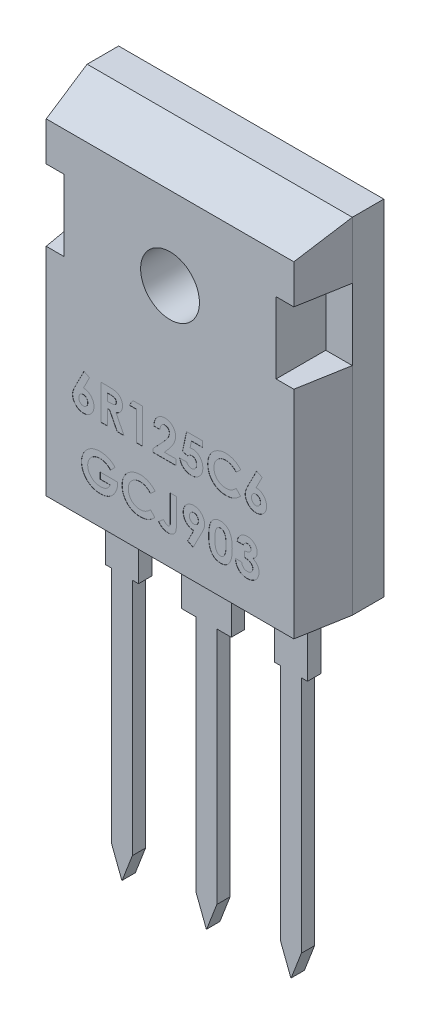
SolidWorks part; units mm, degrees
ref_plane "Front Plane" through (0, 0, 0) normal (0, 0, 1) x (1, 0, 0)
ref_plane "Top Plane" through (0, 0, 0) normal (0, 1, 0) x (1, 0, 0)
ref_plane "Right Plane" through (0, 0, 0) normal (1, 0, 0) x (0, 0, -1)
sketch "Sketch1" plane through (0, 0, 0) normal (0, 0, 1) x (1, 0, 0)
  line L0 (0, 6.1) -> (4.0279, 6.1) construction
  line L1 (-8, 10.4) -> (8, 10.4)
  line L2 (-8, 10.4) -> (-8, -10.4)
  line L3 (-8, -10.4) -> (8, -10.4)
  line L4 (8, 10.4) -> (8, -10.4)
  line L5 (-8, 10.4) -> (8, -10.4) construction
  line L6 (-8, -10.4) -> (8, 10.4) construction
  circle A0 centre (0, 4.325) radius 1.775
  point P0 (0, 0)
  point P10 (0, 0)
  dimension "D3" = 4.3
  dimension "D4" = 3.55
  dimension "D1" = 20.8
  dimension "D2" = 16
extrude "Boss-Extrude1" add sketch "Sketch1" against normal blind 1.9
sketch "Sketch2" plane through (0, 0, 0) normal (0, 0, 1) x (1, 0, 0)
  line L0 (0, 0) -> (0, 12.0952) construction
  line L1 (-8, 6.95) -> (-6.4, 6.95)
  line L2 (-8, 6.95) -> (-8, 2.65) construction
  line L3 (-8, 2.65) -> (-6.4, 2.65)
  line L4 (8, -10.4) -> (8, 10.4)
  line L5 (8, 10.4) -> (-8, 10.4)
  line L6 (-8, 10.4) -> (-8, -10.4)
  line L7 (-8, -10.4) -> (8, -10.4)
  line L8 (8, -10.4) -> (8, 2.65)
  line L9 (8, 10.4) -> (-8, 10.4)
  line L10 (-8, 10.4) -> (-8, 6.95)
  line L11 (-8, -10.4) -> (8, -10.4)
  line L12 (-6.4, 6.95) -> (-6.4, 2.65)
  line L13 (8, 2.65) -> (6.4, 2.65)
  line L14 (6.4, 6.95) -> (6.4, 2.65)
  line L15 (8, 6.95) -> (6.4, 6.95)
  line L16 (8, 6.95) -> (8, 2.65) construction
  line L17 (-8, 6.95) -> (-8, 2.65) construction
  line L18 (-8, 2.65) -> (-8, -10.4)
  line L19 (8, 2.65) -> (8, 6.95) construction
  line L20 (8, 6.95) -> (8, 10.4)
  circle A0 centre (0, 4.325) radius 1.775 construction
  circle A1 centre (0, 4.325) radius 1.775
  dimension "D2" = 12.8
  dimension "D3" = 3.45
  dimension "D4" = 4.3
  dimension "D1" = 0
extrude "Boss-Extrude2" add sketch "Sketch2" along normal blind 3 separate body
chamfer "Chamfer1" distance 3 angle 20 1 edges at (0, 10.4, 3) first distance on face at (0, 10.4, 1.5)
chamfer "Chamfer2" distance 3 angle 10 4 edges at (-8, -3.875, 3) (-8, 8.129, 3) (8, 8.129, 3) (8, -3.875, 3) first distance on face at (-8, -3.875, 1.5) first distance on face at (-8, 8.402, 1.5) first distance on face at (8, 8.402, 1.5) first distance on face at (8, -3.875, 1.5)
sketch "Sketch4" plane through (0, -10.4, 0) normal (0, -1, 0) x (1, 0, 0)
  line L0 (-8, 0) -> (8, 0) construction
  line L1 (-6.1, 0) -> (-4.1, 0)
  line L2 (-6.1, 0) -> (-6.1, 0.8)
  line L3 (-6.1, 0.8) -> (-4.1, 0.8)
  line L4 (-4.1, 0) -> (-4.1, 0.8)
  line L5 (0, 3.7932) -> (0, -3.182) construction
  line L6 (-1.5, 0) -> (1.5, 0)
  line L7 (-1.5, 0) -> (-1.5, 0.8)
  line L8 (-1.5, 0.8) -> (1.5, 0.8)
  line L9 (1.5, 0) -> (1.5, 0.8)
  line L10 (6.1, 0.8) -> (4.1, 0.8)
  line L11 (4.1, 0) -> (4.1, 0.8)
  line L12 (6.1, 0) -> (4.1, 0)
  line L13 (6.1, 0) -> (6.1, 0.8)
  line L14 (-5.1, 0.8) -> (-5.1, 0) construction
  dimension "D1" = 3
  dimension "D2" = 2
  dimension "D3" = 2.6
  dimension "D4" = 0.8
extrude "Boss-Extrude3" add sketch "Sketch4" along normal blind 4 and the other way blind 3
sketch "Sketch5" plane through (0, -14.4, 0) normal (0, -1, 0) x (1, 0, 0)
  line L0 (-1.5, 0) -> (1.5, 0) construction
  line L1 (-0.625, 0.8) -> (0.625, 0.8)
  line L2 (-0.625, 0.8) -> (-0.625, 0)
  line L3 (-0.625, 0) -> (0.625, 0)
  line L4 (0.625, 0.8) -> (0.625, 0)
  line L5 (-0.625, 0.8) -> (0.625, 0) construction
  line L6 (-0.625, 0) -> (0.625, 0.8) construction
  line L7 (0, 0) -> (0, 1.622) construction
  line L8 (1.5, 0.8) -> (-1.5, 0.8) construction
  line L9 (4.1, 0) -> (6.1, 0) construction
  line L10 (4.475, 0.8) -> (5.725, 0.8)
  line L11 (4.475, 0.8) -> (4.475, 0)
  line L12 (4.475, 0) -> (5.725, 0)
  line L13 (5.725, 0.8) -> (5.725, 0)
  line L14 (4.475, 0.8) -> (5.725, 0) construction
  line L15 (4.475, 0) -> (5.725, 0.8) construction
  line L16 (5.1, 0) -> (5.1, 1.3747) construction
  line L17 (6.1, 0.8) -> (4.1, 0.8) construction
  line L18 (-4.475, 0) -> (-5.725, 0)
  line L19 (-5.725, 0.8) -> (-5.725, 0)
  line L20 (-4.475, 0.8) -> (-5.725, 0.8)
  line L21 (-4.475, 0.8) -> (-4.475, 0)
  point P0 (0, 0.4)
  point P13 (5.1, 0.4)
  point P19 (0, 0)
  dimension "D1" = 1.25
  dimension "D2" = 1.25
extrude "Boss-Extrude4" add sketch "Sketch5" along normal blind 16
chamfer "Chamfer3" distance 1.6 angle 21 6 edges at (5.725, -30.4, 0.4) (4.475, -30.4, 0.4) (0.625, -30.4, 0.4) (-0.625, -30.4, 0.4) (-4.475, -30.4, 0.4) (-5.725, -30.4, 0.4) first distance on face at (5.725, -22.4, 0.4) first distance on face at (4.475, -22.4, 0.4) first distance on face at (0.625, -22.4, 0.4) first distance on face at (-0.625, -22.4, 0.4) first distance on face at (-4.475, -22.4, 0.4) first distance on face at (-5.725, -22.4, 0.4)
sketch "Sketch6" plane through (0, 0, 3) normal (0, 0, 1) x (1, 0, 0)
  line L0 (-7.471, -4.9) -> (7.471, -4.9) construction
  line L1 (-7.471, -8.6) -> (7.471, -8.6) construction
  line L2 (0, 0) -> (0, -10.4) construction
  line L3 (-7.471, -10.4) -> (7.471, -10.4) construction
  line L4 (-7.471, 2.65) -> (-7.471, -10.4) construction
  text T0 "6R125C6" font "Century Gothic" height 2.1
  text T1 "GCJ903" font "Century Gothic" height 2.1
  point P9 (0, 0)
  point P10 (0, 0)
  point P11 (0, 0)
  point P12 (-7.471, -4.9)
  point P15 (0, 0)
  point P16 (0, 0)
  dimension "D1" = 1.8
  dimension "D2" = 5.5
extrude "Cut-Extrude1" cut sketch "Sketch6" against normal blind 0.01
sketch "Sketch7" plane through (0, 0, -1.9) normal (0, 0, -1) x (-1, 0, 0)
  line L0 (-6.5, 0.6) -> (-6.5, -7.4)
  line L1 (-6.5, -7.4) -> (6.5, -7.4)
  line L2 (6.5, -7.4) -> (6.5, 0.6)
  line L3 (6.5, 0.6) -> (7.3, 0.6)
  line L4 (7.3, 0.6) -> (7.3, 7.85)
  line L5 (7.3, 7.85) -> (4.1795, 9.2)
  line L6 (4.1795, 9.2) -> (2.875, 9.2)
  line L7 (2.875, 9.2) -> (2.875, 9)
  line L8 (2.875, 9) -> (-2.875, 9)
  line L9 (0, 0) -> (0, 14.454) construction
  line L10 (8, 10.4) -> (8, -10.4) construction
  line L11 (-8, 10.4) -> (8, 10.4) construction
  line L12 (-6.5, 0.6) -> (-7.3, 0.6)
  line L13 (-7.3, 0.6) -> (-7.3, 7.85)
  line L14 (-7.3, 7.85) -> (-4.1795, 9.2)
  line L15 (-4.1795, 9.2) -> (-2.875, 9.2)
  line L16 (-2.875, 9.2) -> (-2.875, 9)
  circle A1 centre (0, 4.325) radius 3.5
  point P23 (0, 9)
  dimension "D10" = 7
  dimension "D1" = 13
  dimension "D2" = 16.6
  dimension "D3" = 0.7
  dimension "D4" = 3.4
  dimension "D5" = 1.2
  dimension "D6" = 2.55
  dimension "D7" = 8
  dimension "D8" = 1.4
  dimension "D9" = 5.75
extrude "Boss-Extrude5" add sketch "Sketch7" along normal blind 0.01
